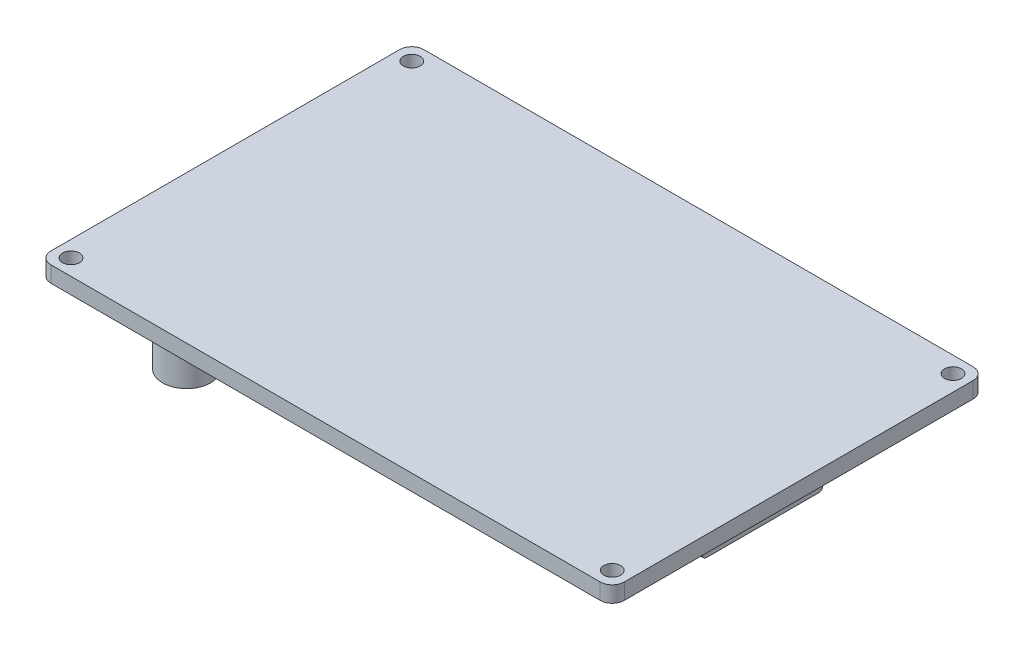
SolidWorks part; units mm, degrees
ref_plane "Front Plane" through (0, 0, 0) normal (0, 0, 1) x (1, 0, 0)
ref_plane "Top Plane" through (0, 0, 0) normal (0, 1, 0) x (1, 0, 0)
ref_plane "Right Plane" through (0, 0, 0) normal (1, 0, 0) x (0, 0, -1)
sketch "Sketch1" plane through (0, 0, 0) normal (0, 1, 0) x (1, 0, 0)
  line L1 (71.5, -46.5) -> (-71.5, -46.5)
  line L2 (71.5, -46.5) -> (71.5, 46.5)
  line L3 (71.5, 46.5) -> (-71.5, 46.5)
  line L4 (-71.5, -46.5) -> (-71.5, 46.5)
  line L5 (71.5, -46.5) -> (-71.5, 46.5) construction
  line L6 (71.5, 46.5) -> (-71.5, -46.5) construction
  point P0 (0, 0)
  dimension "D1" = 143
  dimension "D2" = 93
extrude "lid base" add sketch "Sketch1" along normal blind 4
fillet "Fillet1" radius 3 4 edges at (-71.5, 2, 46.5) (-71.5, 2, -46.5) (71.5, 2, -46.5) (71.5, 2, 46.5)
sketch "Sketch3" plane through (0, 0, 0) normal (0, -1, 0) x (1, 0, 0)
  line L9 (68.1, 43.1) -> (-68.1, 43.1)
  line L10 (-68.1, 43.1) -> (-68.1, -43.1)
  line L11 (-68.1, -43.1) -> (68.1, -43.1)
  line L12 (68.1, -43.1) -> (68.1, 43.1)
  line L13 (68.1, 43.1) -> (-68.1, 43.1)
  line L14 (-68.1, 43.1) -> (-68.1, -43.1)
  line L15 (-68.1, -43.1) -> (68.1, -43.1)
  line L16 (68.1, -43.1) -> (68.1, 43.1)
  line L22 (63.5, 38.5) -> (-63.5, 38.5)
  line L23 (-63.5, 38.5) -> (-63.5, -38.5)
  line L24 (-63.5, -38.5) -> (63.5, -38.5)
  line L25 (63.5, -38.5) -> (63.5, 38.5)
  line L26 (63.5, 38.5) -> (-63.5, 38.5)
  line L27 (-63.5, 38.5) -> (-63.5, -38.5)
  line L28 (-63.5, -38.5) -> (63.5, -38.5)
  line L29 (63.5, -38.5) -> (63.5, 38.5)
  dimension "D1" = 3.4
  dimension "D2" = 8
extrude "lip" add sketch "Sketch3" along normal blind 1.5
sketch "Sketch2" plane through (0, 4, 0) normal (0, 1, 0) x (1, 0, 0)
  circle A0 centre (-67.5, -42.5) radius 2.1
  circle A1 centre (67.5, -42.5) radius 2.1
  circle A2 centre (67.5, 42.5) radius 2.1
  circle A3 centre (-67.5, 42.5) radius 2.1
  dimension "D1" = 4.2
extrude "screws " cut sketch "Sketch2" against normal through all
fillet "lip fillet" radius 2 4 edges at (-63.5, -0.75, 38.5) (-63.5, -0.75, -38.5) (63.5, -0.75, -38.5) (63.5, -0.75, 38.5)
chamfer "lip chamfer" distance 0.5 angle 45 16 edges at (-62.9142, -1.5, 37.9142) (-63.5, -1.5, 0) (-62.9142, -1.5, -37.9142) (0, -1.5, -38.5) (62.9142, -1.5, -37.9142) (63.5, -1.5, 0) (62.9142, -1.5, 37.9142) (0, -1.5, 38.5) (-68.1, -1.5, 0) (-66.0151, -1.5, 41.0151) (0, -1.5, 43.1) (66.0151, -1.5, 41.0151) (68.1, -1.5, 0) (66.0151, -1.5, -41.0151) (0, -1.5, -43.1) (-66.0151, -1.5, -41.0151)
sketch "Sketch4" plane through (0, 4, 0) normal (0, 1, 0) x (1, 0, 0)
  line L0 (62.5, 28) -> (62.5, -28) construction
  line L1 (60.5, 26) -> (33.5, 26) construction
  line L2 (60.5, 26) -> (60.5, -26) construction
  line L3 (60.5, -26) -> (33.5, -26) construction
  line L4 (33.5, 26) -> (33.5, -26) construction
  line L5 (60.5, 26) -> (33.5, -26) construction
  line L6 (60.5, -26) -> (33.5, 26) construction
  line L7 (62.5, -28) -> (31.5, -28) construction
  line L8 (31.5, 28) -> (31.5, -28) construction
  line L9 (62.5, 28) -> (31.5, 28) construction
  line L10 (47, -28) -> (47, -26) construction
  line L11 (62.5, 0) -> (60.5, 0) construction
  line L12 (62.5, 0) -> (31.5, 0) construction
  line L13 (44.5, -26) -> (49.5, -26)
  line L14 (44.5, -26) -> (44.5, -28)
  line L15 (44.5, -28) -> (49.5, -28)
  line L16 (49.5, -26) -> (49.5, -28)
  line L17 (44.5, -26) -> (49.5, -28) construction
  line L18 (44.5, -28) -> (49.5, -26) construction
  line L19 (62.5, -15) -> (60.5, -15)
  line L20 (62.5, -15) -> (62.5, 15)
  line L21 (62.5, 15) -> (60.5, 15)
  line L22 (60.5, -15) -> (60.5, 15)
  line L23 (62.5, -15) -> (60.5, 15) construction
  line L24 (62.5, 15) -> (60.5, -15) construction
  line L25 (47, -28) -> (47, 28) construction
  line L26 (31.5, 15) -> (33.5, -15) construction
  line L27 (31.5, -15) -> (33.5, 15) construction
  line L28 (31.5, 0) -> (33.5, 0) construction
  line L29 (33.5, -15) -> (33.5, 15)
  line L30 (31.5, 15) -> (33.5, 15)
  line L31 (31.5, -15) -> (31.5, 15)
  line L32 (31.5, -15) -> (33.5, -15)
  line L33 (44.5, 28) -> (49.5, 26) construction
  line L34 (44.5, 26) -> (49.5, 28) construction
  line L35 (47, 28) -> (47, 26) construction
  line L36 (49.5, 26) -> (49.5, 28)
  line L37 (44.5, 28) -> (49.5, 28)
  line L38 (44.5, 26) -> (44.5, 28)
  line L39 (44.5, 26) -> (49.5, 26)
  point P0 (47, 0)
  point P14 (61.5, 0)
  point P15 (47, -27)
  point P16 (47, -27)
  point P21 (61.5, 0)
  point P33 (32.5, 0)
  point P39 (47, 27)
  dimension "D1" = 52
  dimension "D2" = 27
  dimension "D3" = 47
  dimension "D5" = 5
  dimension "D6" = 30
  dimension "D7" = 2
  dimension "D4" = 2
extrude "battery pocket" add sketch "Sketch4" against normal blind 14
fillet "bottom pocket fillet" radius 3 8 edges at (44.5, 0, 27) (49.5, 0, 27) (61.5, 0, 15) (61.5, 0, -15) (49.5, 0, -27) (44.5, 0, -27) (32.5, 0, -15) (32.5, 0, 15)
fillet "pocket corner fillets" radius 1 8 edges at (61.5, -10, -15) (61.5, -10, 15) (49.5, -10, 27) (44.5, -10, 27) (32.5, -10, 15) (32.5, -10, -15) (44.5, -10, -27) (49.5, -10, -27)
chamfer "pocket chamfer " distance 0.75 angle 45 28 edges at (50.3787, -0.8787, 26) (43.6213, -0.8787, 26) (49.5, -6, 26) (44.5, -6, 26) (49.2071, -9.7071, 26) (44.7929, -9.7071, 26) (47, -10, 26) (60.5, -0.8787, -15.8787) (60.5, -0.8787, 15.8787) (60.5, -6, -15) (60.5, -6, 15) (60.5, -9.7071, -14.7071) (60.5, -9.7071, 14.7071) (60.5, -10, 0) (43.6213, -0.8787, -26) (50.3787, -0.8787, -26) (44.5, -6, -26) (49.5, -6, -26) (44.7929, -9.7071, -26) (49.2071, -9.7071, -26) (47, -10, -26) (33.5, -0.8787, 15.8787) (33.5, -0.8787, -15.8787) (33.5, -6, 15) (33.5, -6, -15) (33.5, -9.7071, 14.7071) (33.5, -9.7071, -14.7071) (33.5, -10, 0)
sketch "Sketch5" plane through (0, 0, 0) normal (0, -1, 0) x (-1, 0, 0)
  circle A0 centre (51.9184, -29.24) radius 6
  circle A1 centre (51.9184, 29.76) radius 6
extrude "stomp support" add sketch "Sketch5" along normal blind 18.85
sketch "Sketch6" plane through (0, -18.85, 0) normal (0, -1, 0) x (-1, 0, 0)
  circle A0 centre (51.9184, -29.24) radius 3.25
  circle A1 centre (51.9184, 29.76) radius 3.25
  dimension "D1" = 6.5
extrude "screw head place" cut sketch "Sketch6" against normal blind 4
fillet "Fillet4" radius 1.5 2 edges at (-51.9184, 0, 35.24) (-51.9184, 0, -23.76)
